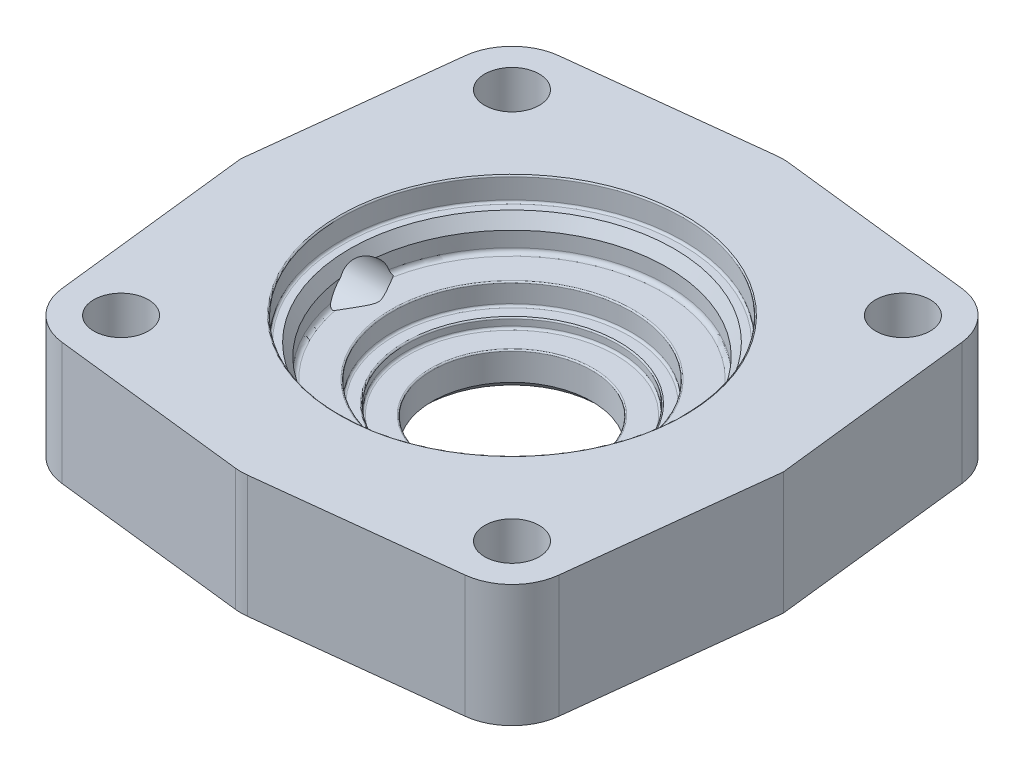
SolidWorks part; units mm, degrees
material "2P Cast Iron"
ref_plane "Front Plane" through (0, 0, 0) normal (0, 0, 1) x (1, 0, 0)
ref_plane "Top Plane" through (0, 0, 0) normal (0, 1, 0) x (1, 0, 0)
ref_plane "Right Plane" through (0, 0, 0) normal (1, 0, 0) x (0, 0, -1)
sketch "Sketch2" plane through (0, 0, 0) normal (0, 1, 0) x (1, 0, 0)
  line L0 (1.1316, 50.8711) -> (37.8816, 46.6858)
  line L1 (-1.1316, 50.8711) -> (-37.8816, 46.6858)
  line L2 (0, -55.2489) -> (0, 70.268) construction
  line L3 (-46.6858, 37.8816) -> (-51, 0)
  line L4 (-51, 0) -> (-46.6858, -37.8816)
  line L5 (-77.9612, 0) -> (67.3997, 0) construction
  line L6 (1.1316, -50.8711) -> (37.8816, -46.6858)
  line L7 (-1.1316, -50.8711) -> (-37.8816, -46.6858)
  line L8 (51, 0) -> (46.6858, -37.8816)
  line L9 (46.6858, 37.8816) -> (51, 0)
  arc A0 (-46.6858, -37.8816) -> (-37.8816, -46.6858) centre (-36.75, -36.75) ccw
  arc A1 (37.8816, -46.6858) -> (46.6858, -37.8816) centre (36.75, -36.75) ccw
  arc A2 (37.8816, 46.6858) -> (46.6858, 37.8816) centre (36.75, 36.75) cw
  arc A3 (-37.8816, 46.6858) -> (-46.6858, 37.8816) centre (-36.75, 36.75) ccw
  arc A4 (1.1316, -50.8711) -> (-1.1316, -50.8711) centre (0, -40.9354) cw
  arc A5 (1.1316, 50.8711) -> (-1.1316, 50.8711) centre (0, 40.9354) ccw
  point P15 (-45.7856, -45.7856)
  point P18 (45.7856, -45.7856)
  point P21 (45.7856, 45.7856)
  point P24 (-45.7856, 45.7856)
  point P27 (0, -51)
  point P30 (0, 51)
  dimension "D4" = 10
  dimension "D5" = 10
  dimension "D1" = 73.5
  dimension "D2" = 73.5
  dimension "D3" = 102
  dimension "D6" = 102
extrude "Boss-Extrude1" add sketch "Sketch2" along normal mid plane 23
sketch "Sketch5" plane through (0, -11.5, 0) normal (0, -1, 0) x (1, 0, 0)
  line L0 (0, -27.936) -> (0, 32.288) construction
  line L1 (-31.053, 0) -> (30.6187, 0) construction
  circle A0 centre (-36.75, 36.75) radius 5.125
  circle A1 centre (36.75, 36.75) radius 5.125
  circle A2 centre (-36.75, -36.75) radius 5.125
  circle A3 centre (36.75, -36.75) radius 5.125
  circle A4 centre (0, 0) radius 51.9723 construction
  dimension "D1" = 10.25
  dimension "D2" = 73.5
  dimension "D3" = 73.5
extrude "Cut-Extrude3" cut sketch "Sketch5" against normal through all
sketch "Sketch4" plane through (0, -11.5, 0) normal (0, -1, 0) x (1, 0, 0)
  circle A0 centre (0, 0) radius 44
  circle A1 centre (0, 0) radius 41.45
  dimension "D1" = 82.9
  dimension "D2" = 88
extrude "Cut-Extrude2" cut sketch "Sketch4" against normal blind 1.75
sketch "Sketch6" plane through (0, 0, 0) normal (1, 0, 0) x (0, 0, -1)
  line L0 (32.25, 11.5) -> (32.25, 7.5)
  line L1 (0, 11.5) -> (37.8816, 11.5) construction
  line L2 (31.85, 7.1) -> (30.5, 7.1)
  line L3 (29.15, 4.7617) -> (29.15, 1.9)
  line L4 (28.35, 1.1) -> (22.75, 1.1)
  line L5 (22.5, 0.85) -> (22.5, -2.5)
  line L6 (22.1, -2.9) -> (20.15, -2.9)
  line L7 (19.9, -3.15) -> (19.9, -4.3)
  line L8 (19.5, -4.7) -> (15.25, -4.7)
  line L9 (15, -4.95) -> (15, -10)
  line L11 (16.5, -11.5) -> (0, -11.5)
  line L12 (32.25, 11.5) -> (0, 11.5)
  line L13 (0, 16.7213) -> (0, -17.807) construction
  line L14 (0, -11.5) -> (0, 11.5)
  line L15 (30.5, 7.1) -> (29.15, 4.7617)
  line L16 (15, -10) -> (16.5, -11.5)
  line L17 (0, -11.5) -> (37.8816, -11.5) construction
  arc A1 (29.15, 1.9) -> (28.35, 1.1) centre (28.35, 1.9) cw
  arc A2 (15.25, -4.7) -> (15, -4.95) centre (15.25, -4.95) ccw
  arc A3 (22.75, 1.1) -> (22.5, 0.85) centre (22.75, 0.85) ccw
  arc A4 (20.15, -2.9) -> (19.9, -3.15) centre (20.15, -3.15) ccw
  arc A5 (19.9, -4.3) -> (19.5, -4.7) centre (19.5, -4.3) cw
  arc A6 (22.5, -2.5) -> (22.1, -2.9) centre (22.1, -2.5) cw
  arc A7 (32.25, 7.5) -> (31.85, 7.1) centre (31.85, 7.5) cw
  dimension "D10" = 61
  dimension "D11" = 0.8
  dimension "D12" = 0.25
  dimension "D13" = 0.25
  dimension "D14" = 0.4
  dimension "D1" = 16.2
  dimension "D2" = 14.4
  dimension "D3" = 10.4
  dimension "D4" = 4.4
  dimension "D5" = 30
  dimension "D6" = 64.5
  dimension "D7" = 58.3
  dimension "D8" = 45
  dimension "D9" = 39.8
  dimension "D15" = 30
  dimension "D16" = 33
  dimension "D17" = 45
revolve "Cut-Revolve1" cut sketch "Sketch6" angle 360 about L13
fillet "Fillet1" radius 0.25 1 edges at (0, 11.5, 32.25)
sketch "Sketch7" plane through (0, 0, 0) normal (0, 0, 1) x (1, 0, 0)
  line L0 (-61.7629, 0) -> (-12.8893, 0) construction
  line L1 (-52.0096, 10) -> (-49.5, 10)
  line L2 (-49.5, 10) -> (-49.5, 5.8)
  line L3 (-49.5, 5.8) -> (-27.985, 5.8)
  line L4 (-27.985, 5.8) -> (-24.5, 0)
  line L6 (-52.0096, 0) -> (-52.0096, 10)
  line L7 (0, 0) -> (0, 20.6198) construction
  line L8 (-52.0096, 0) -> (-24.5, 0)
  dimension "D1" = 59
  dimension "D2" = 11.6
  dimension "D3" = 24.5
  dimension "D4" = 25
  dimension "D5" = 20
  dimension "D6" = 2.5096
revolve "Cut-Revolve2" cut sketch "Sketch7" angle 360 about L8
cosmetic thread "Cosmetic Thread1" parameters "D1"=12, "D2"=13.15
sketch "Sketch8" plane through (0, -11.5, 0) normal (0, -1, 0) x (1, 0, 0)
  circle A0 centre (37.7, 0) radius 2.5
  dimension "D1" = 5
  dimension "D2" = 37.7
sketch "Sketch9" plane through (0, 0, 0) normal (0, 0, 1) x (1, 0, 0)
  line L0 (19.5137, 19.9996) -> (37.7, -11.5) construction
  line L1 (35.2, -11.5) -> (40.2, -11.5) construction
  line L2 (26.4682, 7.954) -> (24.3032, 6.704)
  line L3 (24.3032, 6.704) -> (37.449, -16.0652)
  line L4 (37.449, -16.0652) -> (39.614, -14.8152)
  line L5 (0, 0) -> (0, 16.2994) construction
  line L6 (26.4682, 7.954) -> (39.614, -14.8152)
  dimension "D1" = 5
  dimension "D2" = 30
  dimension "D3" = 3.828
  dimension "D4" = 22.4635
revolve "Cut-Revolve3" cut sketch "Sketch9" angle 360 about L6
